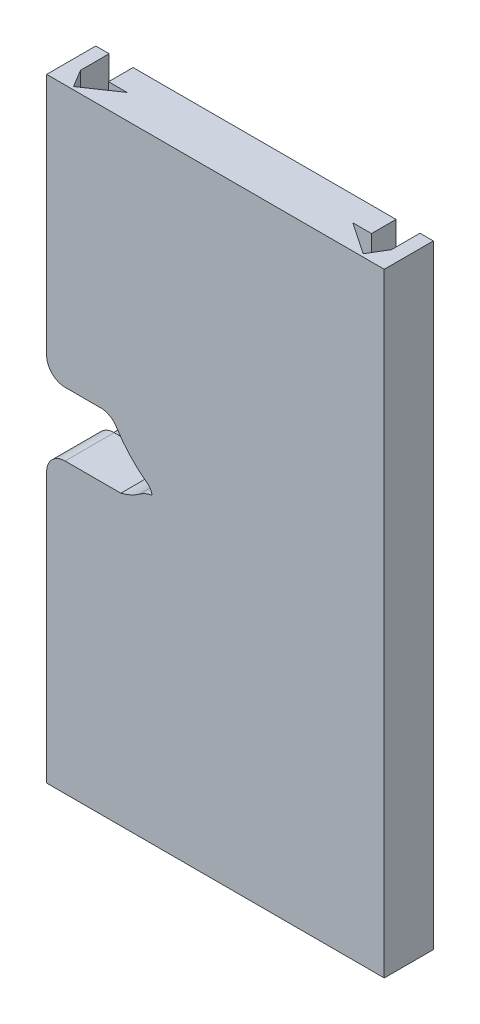
SolidWorks part; units mm, degrees
ref_plane "Front Plane" through (0, 0, 0) normal (0, 0, 1) x (1, 0, 0)
ref_plane "Top Plane" through (0, 0, 0) normal (0, 1, 0) x (1, 0, 0)
ref_plane "Right Plane" through (0, 0, 0) normal (1, 0, 0) x (0, 0, -1)
sketch "Sketch1" plane through (0, 0, 0) normal (0, 1, 0) x (1, 0, 0)
  line L1 (27.5, 4) -> (-27.5, 4)
  line L2 (27.5, 4) -> (27.5, -4)
  line L3 (27.5, -4) -> (-27.5, -4)
  line L4 (-27.5, 4) -> (-27.5, -4)
  line L5 (27.5, 4) -> (-27.5, -4) construction
  line L6 (27.5, -4) -> (-27.5, 4) construction
  point P0 (0, 0)
  dimension "D1" = 55
  dimension "D2" = 8
extrude "Boss-Extrude1" add sketch "Sketch1" along normal blind 100
sketch "Sketch4" plane through (0, 0, -4) normal (0, 0, -1) x (-1, 0, 0)
  line L0 (0, 0) -> (0, 100) construction
  line L1 (-27.5, 0) -> (27.5, 0) construction
  line L2 (-27.5, 100) -> (27.5, 100) construction
  circle A0 centre (0, 65.9483) radius 19
  dimension "D1" = 38
extrude "Cut-Extrude3" cut sketch "Sketch4" against normal blind 3.56
sketch "Sketch5" plane through (0, 0, -4) normal (0, 0, -1) x (-1, 0, 0)
  line L0 (0, 46.9483) -> (27.5, 46.9483)
  line L1 (27.5, 100) -> (27.5, 0) construction
  line L2 (27.5, 46.9483) -> (27.5, 84.9483)
  line L3 (27.5, 84.9483) -> (0, 84.9483)
  circle A0 centre (0, 65.9483) radius 19 construction
  arc A1 (0, 84.9483) -> (0, 46.9483) centre (0, 65.9483) cw
extrude "Cut-Extrude4" cut sketch "Sketch5" against normal blind 2
sketch "Sketch6" plane through (0, 0, -2) normal (0, 0, -1) x (-1, 0, 0)
  line L4 (0, 46.9483) -> (27.5, 46.9483) construction
  line L5 (15.4146, 46.9483) -> (27.5, 46.9483)
  line L7 (16.9393, 57.3424) -> (27.5, 57.3424)
  line L8 (27.5, 46.9483) -> (27.5, 84.9483) construction
  line L9 (27.5, 57.3424) -> (27.5, 46.9483)
  arc A1 (16.9393, 57.3424) -> (9.3165, 49.3893) centre (0, 65.9483) cw
  arc A2 (12.345, 48.3564) -> (15.4146, 46.9483) centre (17.5572, 55.6693) ccw
  arc A3 (10.3352, 49.2045) -> (12.345, 48.3564) centre (9.4429, 44.2848) cw
  spline S0 degree 3 poles (9.3165, 49.3893) (9.6561, 49.3277) (9.9956, 49.2661) (10.3352, 49.2045) knots 0 0 0 0 0.453328 0.453328 0.453328 0.453328
  point P4 (0, 0)
  point P11 (0, 0)
  dimension "D1" = 5
extrude "Cut-Extrude5" cut sketch "Sketch6" against normal blind 16
sketch "Sketch7" plane through (0, 0, -2) normal (0, 0, -1) x (-1, 0, 0)
  line L2 (0, 46.9483) -> (15.4146, 46.9483)
  line L3 (10.3352, 49.2045) -> (9.3165, 49.3893)
  line L4 (0, 46.9483) -> (15.4146, 46.9483)
  line L5 (10.3352, 49.2045) -> (9.3165, 49.3893)
  arc A3 (12.345, 48.3564) -> (15.4146, 46.9483) centre (17.5572, 55.6693) ccw
  arc A4 (12.345, 48.3564) -> (10.3352, 49.2045) centre (9.4429, 44.2848) ccw
  arc A5 (0, 46.9483) -> (9.3165, 49.3893) centre (0, 65.9483) ccw
  arc A6 (12.345, 48.3564) -> (15.4146, 46.9483) centre (17.5572, 55.6693) ccw
  arc A7 (12.345, 48.3564) -> (10.3352, 49.2045) centre (9.4429, 44.2848) ccw
  arc A8 (0, 46.9483) -> (9.3165, 49.3893) centre (0, 65.9483) ccw
  dimension "D1" = 0
extrude "Boss-Extrude2" add sketch "Sketch7" along normal up to surface (2 mm away) up to face at (-4.5, 57.9742, -4)
fillet "Fillet1" radius 3 1 edges at (-27.5, 46.9483, 0)
fillet "Fillet2" radius 3 1 edges at (-27.5, 57.3424, 1)
fillet "Fillet3" radius 3 1 edges at (-16.9393, 57.3424, 1.78)
fillet "Fillet4" radius 2 1 edges at (-9.3165, 49.3893, 1.78)
sketch "Sketch8" plane through (0, 0, -4) normal (0, 0, -1) x (-1, 0, 0)
  line L3 (26.0886, 4.8065) -> (22.2738, 4.8065)
  line L4 (22.2738, 31.4137) -> (22.2738, 4.8065)
  line L6 (24.599, 43.2213) -> (22.2738, 31.4137)
  line L7 (26.0886, 4.8065) -> (26.0886, 48.2217)
  arc A1 (24.599, 43.2213) -> (26.0886, 48.2217) centre (51.5561, 37.9128) cw
  point P0 (26.0886, 48.2217)
extrude "Boss-Extrude3" add sketch "Sketch8" along normal blind 4
sketch "Sketch10" plane through (0, 100, 0) normal (0, 1, 0) x (1, 0, 0)
  line L0 (-25.322, 4) -> (-25.322, -0.6572)
  line L1 (27.5, 4) -> (-27.5, 4) construction
  line L2 (-25.322, -0.6572) -> (-23.5898, -3.5322)
  line L3 (-23.5898, -3.5322) -> (-18.3974, 0)
  line L4 (-18.3974, 0) -> (-21.422, 0)
  line L5 (-21.422, 0) -> (-21.422, 4)
  line L6 (-21.422, 4) -> (-25.322, 4)
  line L7 (-23.372, -2.5374) -> (-20.322, -0.4626) construction
  line L8 (-24.622, -0.4626) -> (-23.372, -2.5374) construction
  line L9 (-20.322, -0.4626) -> (-22.122, -0.4626) construction
  line L10 (-24.622, 4) -> (-24.622, -0.4626) construction
  line L11 (-22.122, -0.4626) -> (-22.122, 4) construction
  line L12 (0, 0) -> (0, 4) construction
  line L13 (25.322, -0.6572) -> (23.5898, -3.5322)
  line L14 (23.5898, -3.5322) -> (18.3974, 0)
  line L15 (18.3974, 0) -> (21.422, 0)
  line L16 (21.422, 0) -> (21.422, 4)
  line L17 (21.422, 4) -> (25.322, 4)
  line L18 (25.322, 4) -> (25.322, -0.6572)
  line M10 (27.5, 4) -> (-27.5, 4)
  dimension "D1" = 0.7
  dimension "D2" = 0.7
  dimension "D3" = 0.7
  dimension "D4" = 0.7
extrude "Cut-Extrude9" cut sketch "Sketch10" against normal blind 39 contours L4 L5 L0 L2 L3 M10
sketch "Sketch11" plane through (0, 100, 0) normal (0, 1, 0) x (1, 0, 0)
  line L5 (21.422, 4) -> (25.322, 4)
  line L7 (18.3974, 0) -> (23.5898, -3.5322)
  line L8 (21.422, 0) -> (18.3974, 0)
  line L9 (21.422, 4) -> (21.422, 0)
  line L10 (25.322, -0.6572) -> (25.322, 4)
  line L11 (23.5898, -3.5322) -> (25.322, -0.6572)
extrude "Cut-Extrude13" cut sketch "Sketch11" against normal blind 108
sketch "Sketch12" plane through (0, 4.8065, 0) normal (0, -1, 0) x (1, 0, 0)
  line L14 (-24.2562, -8) -> (-24.2562, -11.0198) construction
  line L15 (-23.2562, -11.0198) -> (-21.4562, -9.5376)
  line L16 (-21.4562, -9.5376) -> (-23.2562, -9.5376)
  line L17 (-23.2562, -9.5376) -> (-23.2562, -8)
  line L18 (-22.2738, -8) -> (-26.0886, -8) construction
  line L20 (-23.2562, -8) -> (-25.2562, -8)
  line L21 (-25.2562, -8) -> (-25.2562, -9.5376)
  line L24 (-25.2562, -9.5376) -> (-25.2562, -11.0198)
  line L25 (-25.2562, -11.0198) -> (-23.2562, -11.0198)
  point P0 (-24.9392, -6.2723)
  dimension "D1" = 1.8
  dimension "D2" = 2
  dimension "D3" = 2
  dimension "D4" = 2.3317
  dimension "D5" = 3.0198
extrude "Boss-Extrude4" add sketch "Sketch12" against normal blind 18
fillet "Fillet5" radius 0.5 1 edges at (-26.0886, 48.2217, -6)
